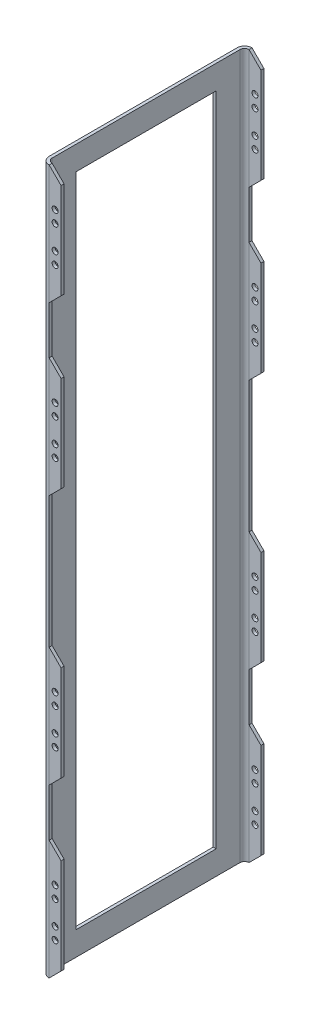
SolidWorks part; units mm, degrees
material "6061-T6 (SS)"
ref_plane "Front Plane" through (0, 0, 0) normal (0, 0, 1) x (1, 0, 0)
ref_plane "Top Plane" through (0, 0, 0) normal (0, 1, 0) x (1, 0, 0)
ref_plane "Right Plane" through (0, 0, 0) normal (1, 0, 0) x (0, 0, -1)
sketch "Sketch1" plane through (0, 0, 0) normal (0, 1, 0) x (1, 0, 0)
  line L0 (-51.5874, 0) -> (49.9999, 0) construction
  line L1 (-49.9999, -49.9999) -> (49.9999, -49.9999) construction
  line L2 (-49.9999, -49.9999) -> (-49.9999, 49.9999) construction
  line L3 (-49.9999, 49.9999) -> (49.9999, 49.9999) construction
  line L4 (49.9999, -49.9999) -> (49.9999, 49.9999) construction
  line L5 (-49.9999, -49.9999) -> (-51.5874, -49.9999) construction
  line L6 (-49.9999, 49.9999) -> (-49.9999, -49.9999)
  line L7 (-41.2686, -53.9686) -> (-41.2686, -52.3812)
  line L8 (-51.5874, 49.9999) -> (-51.5874, -49.9999)
  line L9 (-47.6186, -52.3811) -> (-41.2686, -52.3812)
  line L10 (-47.6186, -53.9686) -> (-41.2686, -53.9686)
  line L11 (-47.6186, 53.9686) -> (-41.2686, 53.9686)
  line L13 (-47.6186, 52.3811) -> (-41.2686, 52.3812)
  line L14 (-41.2686, 53.9686) -> (-41.2686, 52.3812)
  arc A0 (-47.6186, 52.3811) -> (-49.9999, 49.9999) centre (-47.6186, 49.9999) ccw
  arc A1 (-47.6186, 52.3811) -> (-49.9999, 49.9999) centre (-47.6186, 49.9999) ccw
  arc A2 (-47.6186, 53.9686) -> (-51.5874, 49.9999) centre (-47.6186, 49.9999) ccw
  arc A3 (-47.6186, -53.9686) -> (-51.5874, -49.9999) centre (-47.6186, -49.9999) cw
  arc A4 (-47.6186, -52.3811) -> (-49.9999, -49.9999) centre (-47.6186, -49.9999) cw
  arc A5 (-47.6186, -52.3811) -> (-49.9999, -49.9999) centre (-47.6186, -49.9999) cw
  circle A6 centre (0, 0) radius 76.2 construction
  dimension "D9" = 3.9688
  dimension "D7" = 152.4
  dimension "D1" = 49.9999
  dimension "D2" = 49.9999
  dimension "D3" = 6.35
  dimension "D4" = 49.9999
  dimension "D5" = 49.9999
  dimension "D6" = 1.5875
extrude "MainPlateExtrude" add sketch "Sketch1" along normal blind 374.65 contours L9 A4 L6 A0 L13 L14 L11 A2 L8 A3 L10 L7 region at (-50.0459, 0, 0)
sketch "Sketch2" plane through (0, 0, 53.9686) normal (0, 0, 1) x (1, 0, 0)
  line L0 (-47.6186, 374.65) -> (-41.2686, 368.3)
  line L1 (-41.2686, 374.65) -> (-41.2686, 0) construction
  line L2 (-47.6186, 285.75) -> (-41.2686, 279.4)
  line L3 (-47.6186, 374.65) -> (-47.6186, 0) construction
  line L4 (-41.2686, 317.5) -> (-47.6186, 311.15)
  line L5 (-47.6186, 374.65) -> (-41.2686, 374.65)
  line L6 (-41.2686, 374.65) -> (-41.2686, 368.3)
  line L7 (-41.2686, 317.5) -> (-41.2686, 0)
  line L8 (-41.2686, 0) -> (-47.6186, 0)
  line L9 (-47.6186, 0) -> (-41.2686, 6.35)
  line L10 (-47.6186, 63.5) -> (-41.2686, 57.15)
  line L11 (-47.6186, 88.9) -> (-41.2686, 95.25)
  line L12 (-47.6186, 152.4) -> (-41.2686, 146.05)
  line L13 (-47.6186, 222.25) -> (-41.2686, 228.6)
  line L14 (-47.6186, 311.15) -> (-47.6186, 285.75)
  line L15 (-47.6186, 222.25) -> (-47.6186, 152.4)
  line L16 (-47.6186, 88.9) -> (-47.6186, 63.5)
  line M9 (-47.6186, 0) -> (-41.2686, 0)
  line M10 (-41.2686, 0) -> (-41.2686, 374.65)
  line M11 (-41.2686, 374.65) -> (-47.6186, 374.65)
  line M12 (-47.6186, 374.65) -> (-47.6186, 0)
  dimension "D1" = 45
  dimension "D2" = 50.8
  dimension "D3" = 45
  dimension "D4" = 45
  dimension "D5" = 50.8
  dimension "D6" = 45
  dimension "D7" = 25.4
  dimension "D8" = 45
  dimension "D9" = 25.4
  dimension "D10" = 45
  dimension "D11" = 50.8
  dimension "D12" = 45
  dimension "D13" = 50.8
extrude "FlangeCut" cut sketch "Sketch2" against normal blind 107.95 contours L11 L10 M12 M10 | L9 M9 M10 | L13 L12 M12 M10 | L4 L2 M10 M12 | L0 M11 M10 region at (-43.3853, 372.5333, 53.9686) region at (-44.232, 298.45, 53.9686) region at (-44.3555, 187.325, 53.9686) region at (-44.232, 76.2, 53.9686) region at (-43.3853, 2.1167, 53.9686)
sketch "Sketch3" plane through (-51.5874, 0, 0) normal (-1, 0, 0) x (0, 0, 1)
  line L0 (-37.2999, 361.95) -> (-37.2999, 12.7)
  line L1 (-49.9999, 374.65) -> (49.9999, 374.65) construction
  line L2 (-49.9999, 374.65) -> (-49.9999, 0) construction
  line L3 (-49.9999, 0) -> (49.9999, 0) construction
  line L4 (49.9999, 374.65) -> (49.9999, 0) construction
  line L5 (-37.2999, 12.7) -> (37.2999, 12.7)
  line L6 (37.2999, 361.95) -> (37.2999, 12.7)
  line L7 (-37.2999, 361.95) -> (37.2999, 361.95)
  dimension "D1" = 12.7
extrude "Cut-Extrude2" cut sketch "Sketch3" against normal blind 1.5875
sketch "Sketch4" plane through (0, 0, -53.9686) normal (0, 0, -1) x (-1, 0, 0)
  line L0 (41.2686, 342.9) -> (47.6186, 342.9) construction
  line L1 (41.2686, 368.3) -> (41.2686, 317.5) construction
  line L2 (47.6186, 374.65) -> (47.6187, 311.15) construction
  line L3 (41.2686, 254) -> (47.6186, 254) construction
  line L4 (41.2686, 279.4) -> (41.2686, 228.6) construction
  line L5 (47.6186, 285.75) -> (47.6186, 222.25) construction
  line L6 (41.2686, 120.65) -> (47.6186, 120.65) construction
  line L7 (41.2686, 146.05) -> (41.2686, 95.25) construction
  line L8 (47.6186, 152.4) -> (47.6187, 88.9) construction
  line L9 (41.2686, 31.75) -> (47.6186, 31.75) construction
  line L10 (41.2686, 57.15) -> (41.2686, 6.35) construction
  line L11 (47.6186, 63.5) -> (47.6186, 0) construction
  line L12 (44.4436, 31.75) -> (44.4436, 60.325) construction
  line L13 (41.2686, 57.15) -> (47.6186, 63.5) construction
  line L14 (44.4436, 31.75) -> (44.4436, 3.175) construction
  line L15 (41.2686, 6.35) -> (47.6186, 0) construction
  line L16 (44.4436, 120.65) -> (44.4436, 92.075) construction
  line L17 (44.4436, 120.65) -> (44.4436, 149.225) construction
  circle A0 centre (44.4436, 38.1) radius 1.5875
  circle A1 centre (44.4436, 25.4) radius 1.5875
  circle A2 centre (44.4436, 44.45) radius 1.5875
  circle A3 centre (44.4436, 19.05) radius 1.5875
  circle A4 centre (44.4436, 114.3) radius 1.5875
  circle A5 centre (44.4436, 127) radius 1.5875
  circle A6 centre (44.4436, 133.35) radius 1.5875
  circle A7 centre (44.4436, 107.95) radius 1.5875
  circle A8 centre (44.4436, 336.55) radius 1.5875
  circle A9 centre (44.4436, 260.35) radius 1.5875
  circle A10 centre (44.4436, 349.25) radius 1.5875
  circle A11 centre (44.4436, 241.3) radius 1.5875
  circle A12 centre (44.4436, 355.6) radius 1.5875
  circle A13 centre (44.4436, 266.7) radius 1.5875
  circle A14 centre (44.4436, 330.2) radius 1.5875
  circle A15 centre (44.4436, 247.65) radius 1.5875
  dimension "D1" = 3.175
  dimension "D2" = 3.175
  dimension "D5" = 3.175
  dimension "D6" = 3.175
  dimension "D8" = 6.35
  dimension "D9" = 3.175
  dimension "D3" = 6.35
  dimension "D4" = 6.35
  dimension "D7" = 6.35
extrude "Cut-Extrude3" cut sketch "Sketch4" against normal blind 127
